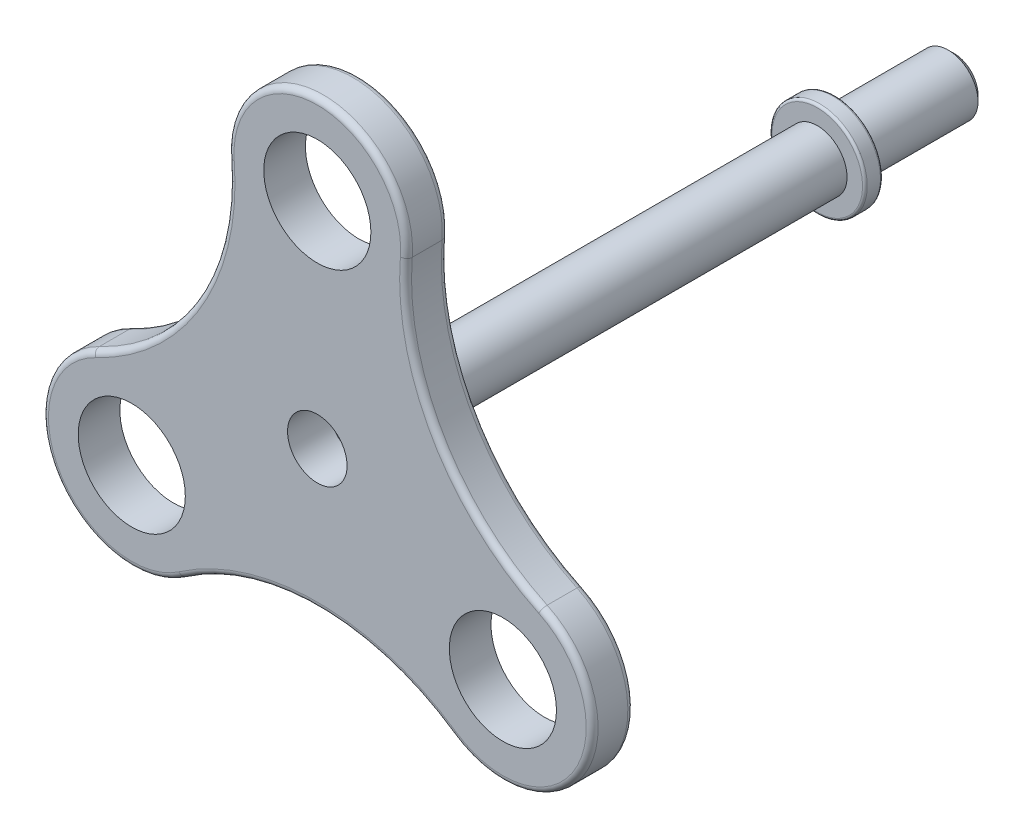
SolidWorks part; units mm, degrees
note: The reader was unsure of these and kept them because the rebuilt part matched: shared geometry of "Sketch1<4>".
material "AISI 1020"
ref_plane "Front Plane" through (0, 0, 0) normal (0, 0, 1) x (1, 0, 0)
ref_plane "Top Plane" through (0, 0, 0) normal (0, 1, 0) x (1, 0, 0)
ref_plane "Right Plane" through (0, 0, 0) normal (1, 0, 0) x (0, 0, -1)
sketch "Sketch1" plane through (0, 0, 0) normal (0, 0, 1) x (1, 0, 0)
  circle A0 centre (0, 18) radius 4.5
  circle A1 centre (0, 18) radius 7.5
  circle A2 centre (15.5885, -9) radius 4.5
  circle A3 centre (15.5885, -9) radius 7.5
  circle A4 centre (-15.5885, -9) radius 4.5
  circle A5 centre (-15.5885, -9) radius 7.5
  arc A6 (7.4766, 17.4075) -> (18.8136, -2.2289) centre (27.4141, 15.8275) ccw
  arc A7 (11.3371, -15.1786) -> (-11.3371, -15.1786) centre (0, -31.655) ccw
  arc A8 (-18.8136, -2.2289) -> (-7.4766, 17.4075) centre (-27.4141, 15.8275) ccw
  circle A9 centre (0, 0) radius 2.5
  point P13 (0, 0)
  dimension "D1" = 15
  dimension "D2" = 9
  dimension "D5" = 20
  dimension "D6" = 3
  dimension "D7" = 5
  dimension "D3" = 18
  dimension "D4" = 3
extrude "Boss-Extrude1" add sketch "Sketch1" along normal blind 3.5 contours A8 A5 A7 A3 A6 A1 | A5 A4 | A3 A2 | A1 A0
extrude "Boss-Extrude3" add sketch "Sketch1<4>" against normal blind 50 separate body contours A9
sketch "Sketch1<4>" plane through (0, 0, 0) normal (0, 0, 1) x (1, 0, 0) same geometry as "Sketch1"
sketch "Sketch5" plane through (0, 0, -50) normal (0, 0, -1) x (-1, 0, 0)
  circle A0 centre (0, 0) radius 4
  circle M1 centre (0, 0) radius 2.5
  dimension "D1" = 8
extrude "Boss-Extrude4" add sketch "Sketch5" along direction (0, 0, 1) on the side against the normal blind 1.5 from offset 10 contours A0 M1 | M1 offset against normal yes
sketch "Sketch6" plane through (0, 0, 0) normal (1, 0, 0) x (0, 0, -1)
  line L0 (42.5, 0) -> (47.5, 0) construction
  line L1 (42.5, 0.75) -> (47.5, 0.75)
  line L2 (42.5, -0.75) -> (47.5, -0.75)
  line L3 (50, -2.5) -> (50, 2.5) construction
  arc A0 (42.5, 0.75) -> (42.5, -0.75) centre (42.5, 0) ccw
  arc A1 (47.5, -0.75) -> (47.5, 0.75) centre (47.5, 0) ccw
  point P2 (45, 0)
  dimension "D1" = 5
  dimension "D2" = 5
  dimension "D3" = 1.5
extrude "Cut-Extrude2" cut sketch "Sketch6" along normal offset from surface (3.146 mm away) 0.5 from offset 5 contours A1 L1 A0 L2 offset against normal yes
chamfer "Chamfer1" distance 0.5 angle 45 1 edges at (2.5, 0, -50)
fillet "Fillet1" radius 0.2 2 edges at (-4, 0, -40) (-4, 0, -38.5)
fillet "Fillet2" radius 0.5 12 edges at (-22.0836, -12.75, 0) (-22.0836, -12.75, 3.5) (0, -11.655, 0) (0, -11.655, 3.5) (22.0836, -12.75, 0) (22.0836, -12.75, 3.5) (10.0935, 5.8275, 0) (10.0935, 5.8275, 3.5) (0, 25.5, 0) (0, 25.5, 3.5) (-10.0935, 5.8275, 0) (-10.0935, 5.8275, 3.5)
